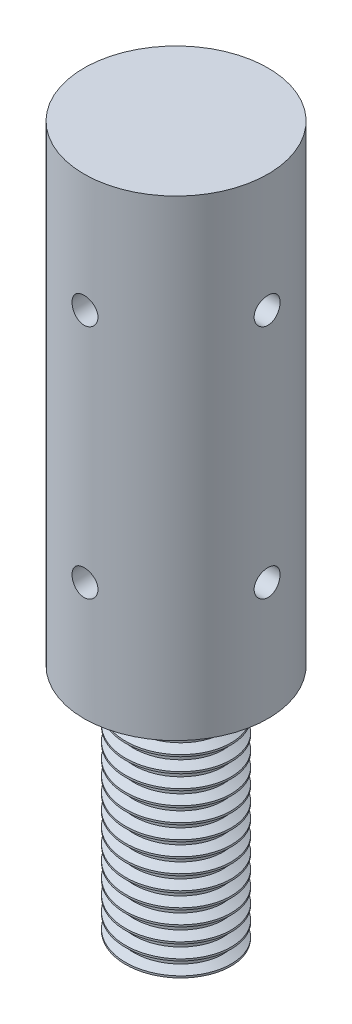
SolidWorks part; units mm, degrees
ref_plane "Front Plane" through (0, 0, 0) normal (0, 0, 1) x (1, 0, 0)
ref_plane "Top Plane" through (0, 0, 0) normal (0, 1, 0) x (1, 0, 0)
ref_plane "Right Plane" through (0, 0, 0) normal (1, 0, 0) x (0, 0, -1)
sketch "Sketch1" plane through (0, 0, 0) normal (0, 1, 0) x (1, 0, 0)
  circle A0 centre (0, 0) radius 4.953
  dimension "D1" = 9.906
extrude "Boss-Extrude1" add sketch "Sketch1" along normal blind 25.4
sketch "Sketch2" plane through (0, 0, 0) normal (0, -1, 0) x (1, 0, 0)
  circle A0 centre (0, 0) radius 2.413
  dimension "D1" = 4.826
extrude "Boss-Extrude2" add sketch "Sketch2" along normal blind 12.7
thread "Thread3" start angle 0, offset 1, length 0, pitch 0.7937, diameter 4.826
ref_plane "Plane6" through (2.413, -13.7, 0) normal (0, 0, 1) x (1, 0, 0)
sketch "Thread Profile6" plane through (2.413, -13.7, 0) normal (0, 0, 1) x (1, 0, 0)
  line L0 (0, 0) -> (0, 0.7937) construction
  line L1 (0, 0) -> (0.4296, 0.248)
  line L2 (0.4296, 0.248) -> (0.4296, 0.3473)
  line L3 (0.4296, 0.3473) -> (0, 0.5953)
  line L4 (0.4296, 0.2977) -> (0, 0.2977) construction
  line L11 (0, 0) -> (0, 0.5953)
  point P2 (0, 0)
  dimension "Pitch" = 0.7937
  dimension "Profile_Angle" = 60
  dimension "Profile_Land" = 0.0992
  dimension "Profile_Height" = 0.4296
ref_plane "Plane7" through (-4.953, 0, 0) normal (-1, 0, 0) x (0, 0, 1)
sketch "Sketch3" plane through (-4.953, 0, 0) normal (-1, 0, 0) x (0, 0, 1)
  line L0 (0, 0) -> (0, 25.4) construction
  circle A0 centre (0, 6.35) radius 0.6985
  circle A1 centre (0, 19.05) radius 0.6985
  dimension "D2" = 1.397
  dimension "D3" = 1.397
  dimension "D1" = 25.4
  dimension "D4" = 6.35
  dimension "D5" = 12.7
extrude "Cut-Extrude1" cut sketch "Sketch3" against normal blind 3.175
pattern_circular "CirPattern1" count 4 over 360 about axis through (0, 0, 0) along (0, 1, 0) of "Cut-Extrude1"
